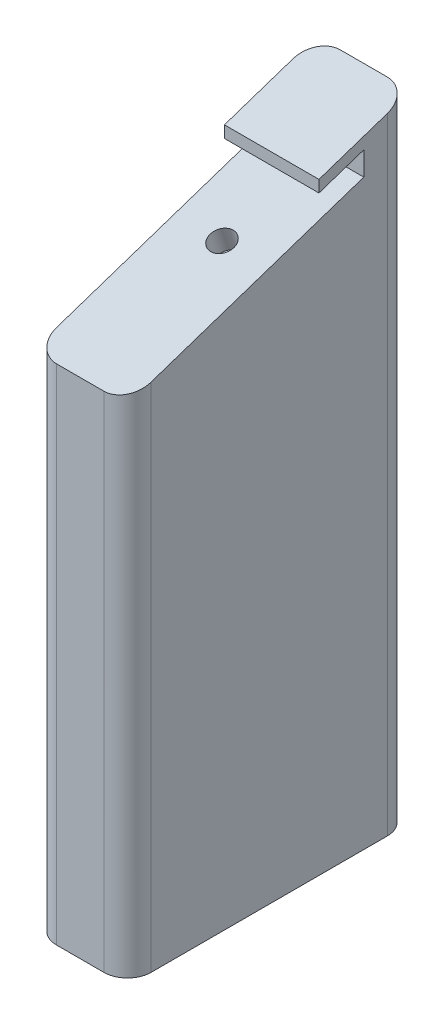
SolidWorks part; units mm, degrees
material "ABS"
ref_plane "Front Plane" through (0, 0, 0) normal (0, 0, 1) x (1, 0, 0)
ref_plane "Top Plane" through (0, 0, 0) normal (0, 1, 0) x (1, 0, 0)
ref_plane "Right Plane" through (0, 0, 0) normal (1, 0, 0) x (0, 0, -1)
sketch "Sketch1" plane through (0, 0, 0) normal (0, 1, 0) x (1, 0, 0)
  line L0 (-12.7, 25.4) -> (12.7, 25.4)
  line L1 (-12.7, -38.1) -> (12.7, -38.1)
  line L2 (-12.7, -38.1) -> (-12.7, 38.1)
  line L3 (-12.7, 38.1) -> (12.7, 38.1)
  line L4 (12.7, -38.1) -> (12.7, 38.1)
  line L5 (-12.7, -38.1) -> (12.7, 38.1) construction
  line L6 (-12.7, 38.1) -> (12.7, -38.1) construction
  point P0 (0, 0)
  dimension "D3" = 12.7
  dimension "D1" = 25.4
  dimension "D2" = 76.2
extrude "Boss-Extrude1" add sketch "Sketch1" along normal blind 160.782 contours L1 L4 L0 L2 | L0 L4 L3 L2 region at (0, 0, -31.75) region at (0, 0, 6.35)
sketch "Sketch4" plane through (12.7, 0, 0) normal (1, 0, 0) x (0, 0, -1)
  line L0 (38.1, 160.782) -> (-38.1, 160.782)
  line L1 (-38.1, 160.782) -> (-38.1, 135.2858)
  line L3 (-38.1, 135.2858) -> (38.1, 160.782)
  line L4 (-38.1, 135.2858) -> (38.1, 135.2858) construction
  line L7 (-38.1, 160.782) -> (-38.1, 0) construction
  line L8 (38.1, 160.782) -> (38.1, 0) construction
  point P4 (38.1, 160.782)
  point P6 (-38.1, 160.782)
  point P7 (-38.1, 135.2752)
  point P11 (-38.1, 160.782)
  point P13 (38.1, 160.782)
  point P14 (48.3551, 160.782)
  point P15 (38.1, 160.782)
  point P16 (38.1, 160.782)
  point P17 (0, 0)
  point P20 (38.1, 135.2858)
  dimension "D1" = 18.5
extrude "Cut-Extrude2" cut sketch "Sketch4" against normal through all both and the other way through all
sketch "Sketch5" plane through (0, 133.1295, 44.5445) normal (0, 0.9483, 0.3173) x (1, 0, 0)
  line L0 (0, 87.148) -> (0, 6.7957) construction
  line L1 (12.7, 87.148) -> (-12.7, 87.148) construction
  line L2 (-12.7, 6.7957) -> (12.7, 6.7957) construction
  line L3 (-12.7, 46.9719) -> (12.7, 46.9719) construction
  line L4 (-12.7, 6.7957) -> (-12.7, 87.148) construction
  line L5 (12.7, 87.148) -> (12.7, 6.7957) construction
  circle A0 centre (0, 46.9719) radius 3.175
  dimension "D1" = 6.35
extrude "Cut-Extrude3" cut sketch "Sketch5" against normal blind 6.35
ref_point "Point1"
extrude "Boss-Extrude2" add sketch "Sketch1<5>" along normal blind 9.525 from surface contours L0 L4 L3 L2 region at (0, 0, -31.75) starting at face at (0, 147.0265, 3.0109)
sketch "Sketch1<5>" plane through (0, 0, 0) normal (0, 1, 0) x (1, 0, 0) same geometry as "Sketch1"
sketch "Sketch8" plane through (0, 0, -25.4) normal (0, 0, 1) x (1, 0, 0)
  line L0 (12.7, 166.0576) -> (12.7, 156.5326) construction
  line L1 (-12.7, 166.0576) -> (12.7, 166.0576)
  line L2 (-12.7, 166.0576) -> (-12.7, 162.8826)
  line L3 (-12.7, 162.8826) -> (12.7, 162.8826)
  line L4 (12.7, 166.0576) -> (12.7, 162.8826)
  dimension "D1" = 3.175
extrude "Boss-Extrude3" add sketch "Sketch8" along direction (0, 0.3173, -0.9483) on the side of the normal blind 12.7
fillet "Fillet1" radius 6.35 4 edges at (-12.7, 85.1535, -38.1) (-12.7, 67.6429, 38.1) (12.7, 67.6429, 38.1)
